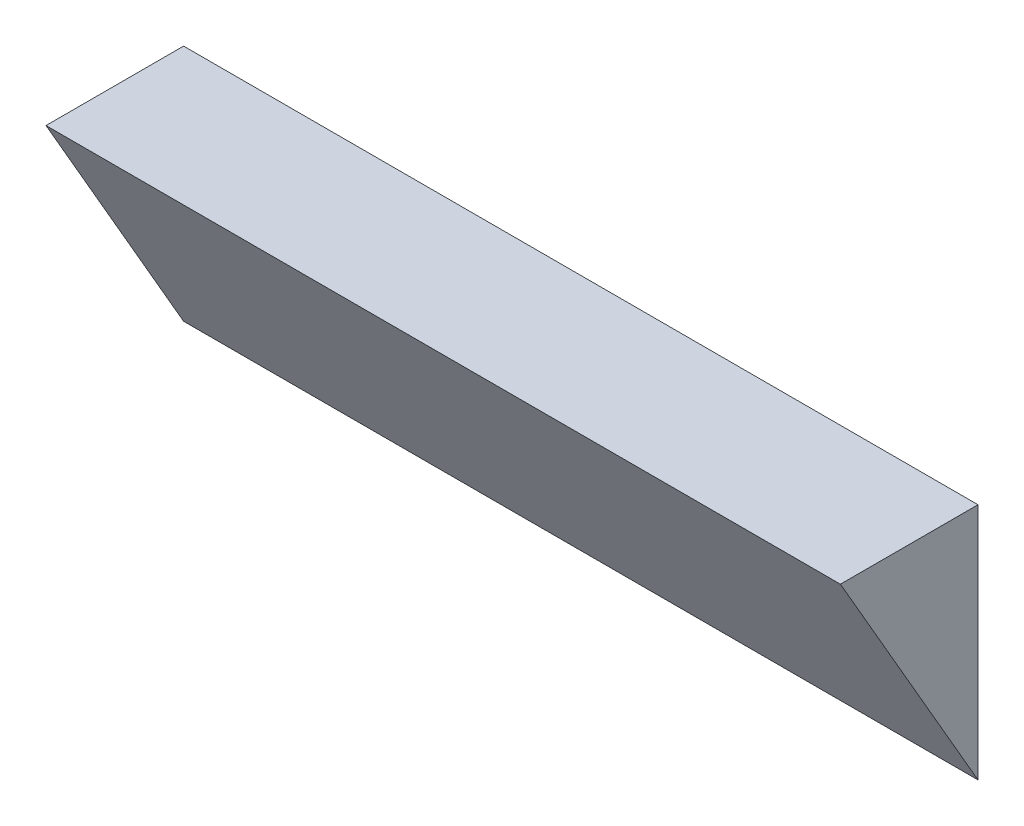
SolidWorks part; units mm, degrees
ref_plane "Front Plane" through (0, 0, 0) normal (0, 0, 1) x (1, 0, 0)
ref_plane "Top Plane" through (0, 0, 0) normal (0, 1, 0) x (1, 0, 0)
ref_plane "Right Plane" through (0, 0, 0) normal (1, 0, 0) x (0, 0, -1)
other "Bounding Box"
ref_plane "Default Plane" through (13.8565, 3.175, 6.7999) normal (0, -1, 0) x (-1, 0, 0)
sketch "Sketch1" plane through (0, 0, 0) normal (1, 0, 0) x (0, 0, -1)
  line L0 (0, 0) -> (0, -38.1)
  line L1 (0, -38.1) -> (-21.997, 0)
  line L2 (-21.997, 0) -> (0, 0)
  dimension "D1" = 30
  dimension "D2" = 38.1
extrude "Boss-Extrude1" add sketch "Sketch1" along normal blind 127
